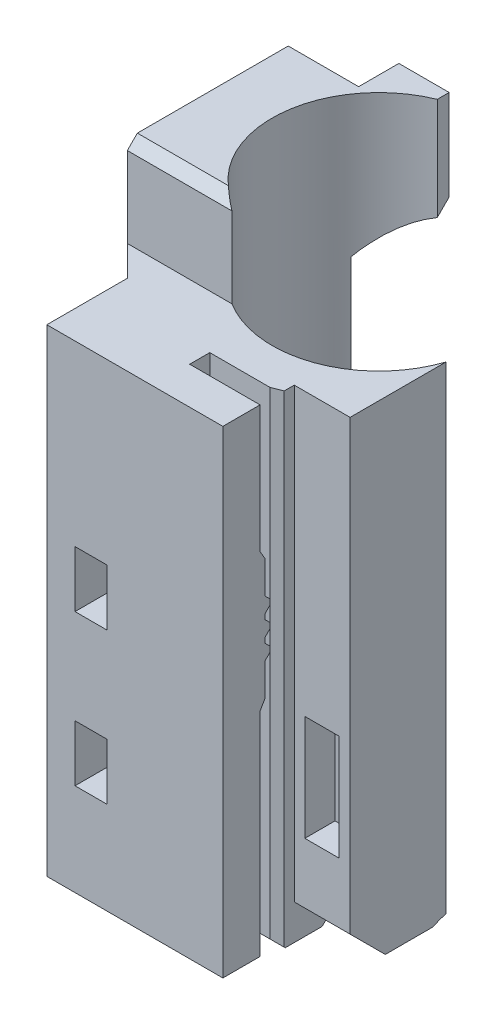
SolidWorks part; units mm, degrees
material "ABS"
ref_plane "Front Plane" through (0, 0, 0) normal (0, 0, 1) x (1, 0, 0)
ref_plane "Top Plane" through (0, 0, 0) normal (0, 1, 0) x (1, 0, 0)
ref_plane "Right Plane" through (0, 0, 0) normal (1, 0, 0) x (0, 0, -1)
sketch "Sketch2" plane through (0, 0, 0) normal (0, 1, 0) x (1, 0, 0)
  line L0 (11.943, 4.3896) -> (12, 3.8141) construction
  line L1 (12, 3.8141) -> (12, -12.9) construction
  line L2 (10.05, -12.9) -> (4.5, -12.9)
  line L3 (4.5, -12.9) -> (4.5, -20)
  line L4 (4.5, -20) -> (-13, -20)
  line L5 (-13, -20) -> (-13, 11)
  line L6 (10.05, -3.3701) -> (10.05, -12.9)
  line L7 (9.6484, 4.3896) -> (11.943, 4.3896) construction
  line L8 (-13, 11) -> (-4, 11)
  line L9 (-4, 11) -> (-4, 9.8163)
  circle A0 centre (0, 0) radius 10.5 construction
  arc A1 (-4, 9.8163) -> (10.05, -3.3701) centre (0, 0) ccw
  dimension "D1" = 21
  dimension "D2" = 0.1
  dimension "D3" = 4.5
  dimension "D4" = 12
  dimension "D5" = 13
  dimension "D6" = 12.9
  dimension "D7" = 20
  dimension "D8" = 11
  dimension "D9" = 4
  dimension "D10" = 10.05
extrude "Boss-Extrude1" add sketch "Sketch2" along normal blind 37 and the other way blind 20
sketch "Sketch3" plane through (0, 0, 0) normal (0, -1, 0) x (1, 0, 0)
  circle A0 centre (0, 0) radius 10.5
  dimension "D1" = 21
extrude "Cut-Extrude1" [suppressed] cut sketch "Sketch3" against normal blind 20 from offset 4 offset against normal yes
mirror "Mirror1" [suppressed] about plane through (0, 0, 0) normal (0, 1, 0)
sketch "Sketch4" plane through (0, 37, 0) normal (0, -1, 0) x (1, 0, 0)
  line L0 (4.5, 20) -> (4.5, 12.9) construction
  line L1 (-13, 20) -> (4.5, 20)
  line L2 (-13, 20) -> (-13, 9.9962)
  line L3 (-13, 9.9962) -> (4.5, 9.9962)
  line L4 (4.5, 20) -> (4.5, 9.9962)
extrude "Cut-Extrude3" [suppressed] cut sketch "Sketch4" along normal blind 11
sketch "Sketch5" plane through (4.5, 0, 0) normal (1, 0, 0) x (0, 0, -1)
  line L0 (-15.8, 5.718) -> (-15.3, 6.218)
  line L1 (-14.3, -20) -> (-16.3, -20)
  line L2 (-14.3, -20) -> (-14.3, 37)
  line L3 (-16.3, 37) -> (-14.3, 37)
  line L4 (-15.8, 2.5) -> (-15.8, 5.718)
  line L5 (-15.3, 6.218) -> (-15.3, 6.718)
  line L6 (-15.3, 6.718) -> (-15.8, 7.218)
  line L7 (-15.8, 9.782) -> (-15.3, 10.282)
  line L8 (-15.3, 10.282) -> (-15.3, 10.782)
  line L9 (-15.3, 10.782) -> (-15.8, 11.282)
  line L10 (-15.8, 7.75) -> (-15.3, 8.25)
  line L11 (-15.3, 8.25) -> (-15.3, 8.75)
  line L12 (-15.3, 8.75) -> (-15.8, 9.25)
  line L13 (-15.8, 9.25) -> (-15.8, 9.782)
  line L14 (-15.8, 2.5) -> (-16.3, 1.634)
  line L15 (-15.8, 7.218) -> (-15.8, 7.75)
  line L16 (-16.3, 1.634) -> (-16.3, -20)
  line L17 (-15.8, 11.282) -> (-15.8, 14.5)
  line L18 (-15.8, 14.5) -> (-16.3, 15.366)
  line L19 (-20, -20) -> (-12.9, -20) construction
  line L20 (11, 8.5) -> (-15.3, 8.5) construction
  line L21 (-16.3, 15.366) -> (-16.3, 37)
  line L22 (-20, 37) -> (-12.9, 37) construction
  line L23 (11, -20) -> (11, 37) construction
  dimension "D1" = 0.5
  dimension "D2" = 0.5
  dimension "D3" = 2.032
  dimension "D4" = 1.5
  dimension "D5" = 2
  dimension "D6" = 14.3
  dimension "D7" = 6
  dimension "D8" = 150
extrude "Cut-Extrude5" cut sketch "Sketch5" against normal blind 7
chamfer "Chamfer1" [suppressed] distance 1.2 angle 45
chamfer "Chamfer2" distance 3.5 angle 45 1 edges at (7.275, -20, 12.9)
chamfer "Chamfer3" distance 0.5 angle 45 9 edges at (1, -20, 14.3) (-9.7101, -20, 4.2514) (-4, -20, -10.4082) (-8.5, -20, -11) (-13, -20, 4.5) (-4.25, -20, 20) (4.5, -20, 18.15) (1, -20, 16.3) (-2.5, -20, 15.3)
sketch "Sketch6" plane through (-13, 0, 0) normal (-1, 0, 0) x (0, 0, 1)
  line L0 (13, 7.5) -> (13, -7.5) construction
  line L1 (0, 0) -> (13, 0) construction
  circle A0 centre (13, 7.5) radius 1.55
  circle A1 centre (13, -7.5) radius 1.55
  dimension "D2" = 3.1
  dimension "D1" = 15
  dimension "D3" = 13
extrude "Cut-Extrude6" cut sketch "Sketch6" against normal blind 10
sketch "Sketch7" plane through (-13, 0, 0) normal (-1, 0, 0) x (0, 0, 1)
  line L0 (21.9673, -4.7) -> (21.9673, -10.3)
  line L1 (9.7668, -7.5) -> (11.3834, -10.3)
  line L2 (11.3834, -10.3) -> (21.9673, -10.3)
  line L3 (11.3834, 4.7) -> (9.5598, 7.5)
  line L4 (21.9673, 4.7) -> (11.3834, 4.7)
  line L5 (21.9673, -4.7) -> (11.3834, -4.7)
  line L6 (11.3834, -4.7) -> (9.7668, -7.5)
  line L7 (-3, 8.5) -> (19.4531, 8.5) construction
  line L9 (11.3834, 10.3) -> (21.9673, 10.3)
  line L10 (13.3663, -12.4655) -> (15.2648, -9.1772) construction
  line L11 (16.8557, -8.5783) -> (15.7995, -6.7488) construction
  line L12 (9.5598, 7.5) -> (11.3834, 10.3)
  line L13 (21.9673, 4.7) -> (21.9673, 10.3)
  circle A0 centre (13, -7.5) radius 2.8 construction
  circle A1 centre (13, -7.5) radius 1.55 construction
  circle A2 centre (13, 7.5) radius 2.8 construction
  circle A3 centre (13, 7.5) radius 1.55 construction
  dimension "D1" = 5.6
extrude "Cut-Extrude7" cut sketch "Sketch7" against normal blind 3.2 from offset 2.8 offset against normal yes
sketch "Sketch9" plane through (-13, 0, 0) normal (-1, 0, 0) x (0, 0, 1)
  line L0 (-11, 28) -> (-6, 23)
  line L1 (-11, -19.5) -> (-11, 37) construction
  line L2 (-6, 23) -> (-6, -20)
  line L3 (-11, -20) -> (20, -20) construction
  line L4 (-6, -20) -> (-11, -20)
  line L5 (-11, -20) -> (-11, 28)
  line L6 (-11, 37) -> (20, 37) construction
  dimension "D1" = 9
  dimension "D2" = 6
  dimension "D3" = 45
extrude "Cut-Extrude9" cut sketch "Sketch9" against normal blind 10
sketch "Sketch12" plane through (-13, 0, 0) normal (-1, 0, 0) x (0, 0, 1)
  line L0 (9, 37) -> (9, 22.9518)
  line L1 (-11, 37) -> (20, 37) construction
  line L2 (9, 22.9518) -> (-5.9518, 22.9518)
  line L3 (-6, 23) -> (-11, 28) construction
  line L4 (-5.9518, 22.9518) -> (-11, 28)
  line L5 (-11, 28) -> (-11, 37)
  line L6 (-11, 37) -> (9, 37)
  dimension "D1" = 20
extrude "Boss-Extrude2" add sketch "Sketch12" along normal blind 3
sketch "Sketch10" plane through (0, 0, -11) normal (0, 0, -1) x (-1, 0, 0)
  line L1 (16, 37) -> (9, 37)
  line L2 (16, 37) -> (16, 28.8)
  line L3 (16, 28.8) -> (9, 28.8)
  line L4 (9, 37) -> (9, 28.8)
  line L5 (16, 37) -> (16, 28) construction
  line L6 (4, 28) -> (16, 28) construction
  line L7 (4, 37) -> (16, 37) construction
  dimension "D1" = 7
  dimension "D3" = 0.8
extrude "Cut-Extrude10" cut sketch "Sketch10" against normal blind 4
sketch "Sketch11" plane through (-16, 0, 0) normal (-1, 0, 0) x (0, 0, 1)
  line L0 (-7, 28.8) -> (-11, 28.8) construction
  line L2 (-11, 28) -> (-11, 28.8) construction
  circle A0 centre (-4, 26.3) radius 1.25
  circle A1 centre (6, 26.3) radius 1.25
  dimension "D3" = 10
  dimension "D4" = 2.5
  dimension "D1" = 2.5
  dimension "D2" = 7
extrude "Cut-Extrude11" cut sketch "Sketch11" against normal blind 4
chamfer "Chamfer4" distance 3 angle 45 2 edges at (-13, 22.9518, 1.5241)
sketch "Sketch13" plane through (0, 37, 0) normal (0, 1, 0) x (1, 0, 0)
  line L0 (-16, -9) -> (0, -9)
  line L1 (0, -9) -> (0, 6.4112)
  line L2 (-16, -9) -> (-16, -20)
  line L3 (12, -20) -> (-16, -20)
  line L4 (0, 6.4112) -> (12, 6.4112)
  line L5 (12, -20) -> (12, 6.4112)
  line L7 (-13, -20) -> (4.5, -20) construction
extrude "Cut-Extrude12" cut sketch "Sketch13" against normal blind 9
chamfer "Chamfer5" distance 1 angle 45 1 edges at (-10.8, 37, 9)
sketch "Sketch14" plane through (0, 0, 12.9) normal (0, 0, 1) x (1, 0, 0)
  line L1 (8.95, -10.5) -> (5.55, -10.5)
  line L2 (8.95, -10.5) -> (8.95, 0)
  line L3 (8.95, 0) -> (5.55, 0)
  line L4 (5.55, -10.5) -> (5.55, 0)
  line L5 (8.95, -10.5) -> (5.55, 0) construction
  line L6 (8.95, 0) -> (5.55, -10.5) construction
  line L8 (10.05, -16.5) -> (10.05, 28) construction
  point P0 (7.25, -5.25)
  dimension "D1" = 3.4
  dimension "D2" = 1.1
  dimension "D3" = 10.5
extrude "Cut-Extrude13" cut sketch "Sketch14" against normal blind 3
chamfer "Chamfer6" distance 1 angle 45 1 edges
chamfer "Chamfer7" distance 0.4 distance2 1 1 edges at (4.5, 4.25, 14.3) first distance on face at (4.5, -5.6889, 12.6141)
